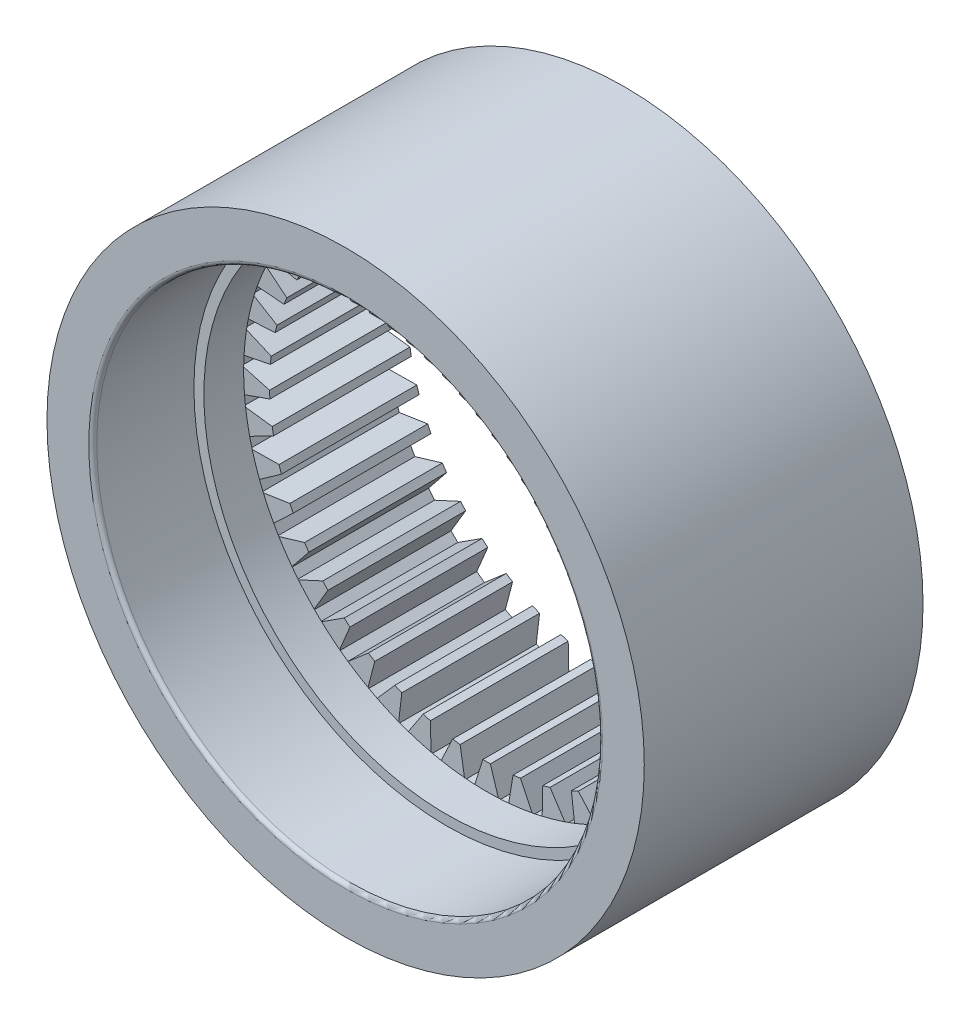
SolidWorks part; units mm, degrees
ref_plane "Plan de face" through (0, 0, 0) normal (0, 0, 1) x (1, 0, 0)
ref_plane "Plan de dessus" through (0, 0, 0) normal (0, 1, 0) x (1, 0, 0)
ref_plane "Plan de droite" through (0, 0, 0) normal (1, 0, 0) x (0, 0, -1)
sketch "Esquisse1" plane through (0, 0, 0) normal (0, 0, 1) x (1, 0, 0)
  circle A0 centre (0, 0) radius 75
  dimension "D1" = 150
extrude "Boss.-Extru.1" add sketch "Esquisse1" along normal blind 70
sketch "Esquisse2" plane through (0, 0, 70) normal (0, 0, 1) x (1, 0, 0)
  circle A0 centre (0, 0) radius 63.5
  dimension "D1" = 127
extrude "Enlèv. mat.-Extru.1" cut sketch "Esquisse2" against normal blind 25.4
sketch "Esquisse3" plane through (0, 0, 44.6) normal (0, 0, 1) x (1, 0, 0)
  circle A0 centre (0, 0) radius 54.5
  dimension "D1" = 109
extrude "Enlèv. mat.-Extru.3" cut sketch "Esquisse3" against normal through all
sketch "Esquisse4" plane through (0, 0, 44.6) normal (0, 0, 1) x (1, 0, 0)
  line L0 (0, 0) -> (0, 94.0639) construction
  line L1 (0, 0) -> (-2.8523, 54.4253)
  line L2 (-2.8523, 54.4253) -> (-1.2, 61.4253)
  line L3 (-1.2, 61.4253) -> (1.2, 61.4253)
  line L4 (2.8523, 54.4253) -> (1.2, 61.4253)
  line L5 (0, 0) -> (2.8523, 54.4253)
  line L6 (2.8523, 54.4253) -> (-9.2115, 54.4253) construction
  circle A0 centre (0, 0) radius 54.5 construction
  point P9 (0, 61.4253)
  dimension "D1" = 3
  dimension "D2" = 1.2
  dimension "10" = 7
extrude "Enlèv. mat.-Extru.4" cut sketch "Esquisse4" against normal blind 70 from offset 10 offset against normal yes
ref_axis "Axe1" through (0, 0, 70) along (0, 0, -1)
pattern_circular "Répétition circulaire1" count 45 every 8 about axis through (0, 0, 70) along (0, 0, -1) of "Enlèv. mat.-Extru.4"
sketch "Esquisse5" plane through (0, 0, 70) normal (0, 0, 1) x (1, 0, 0)
  circle A0 centre (0, 0) radius 61
  dimension "D1" = 122
extrude "Enlèv. mat.-Extru.5" cut sketch "Esquisse5" against normal blind 10 from offset 25.4 offset against normal yes
fillet "Congé1" radius 1 1 edges at (63.5, 0, 70)
ref_plane "Plan1" through (55.7347, 25.8485, 34.6) normal (-0.4384, 0.8988, 0) x (0.8988, 0.4384, 0)
equation "\"D\"= 150"
equation "\"Roulepiss\"= 25.4"
equation "\"episs\"=70"
equation "\"RoulDext\"= 127"
equation "\"D1@Esquisse1\"=\"D\""
equation "\"D1@Boss.-Extru.1\"=\"episs\""
equation "\"D1@Esquisse2\"=\"RoulDext\""
equation "\"D1@Enlèv. mat.-Extru.1\"=\"Roulepiss\""
equation "\"RoulDint\"= 109"
equation "\"D1@Esquisse3\"=\"RoulDint\""
equation "\"D1@Enlèv. mat.-Extru.4\"=\"episs\""
equation "\"D1@Enlèv. mat.-Extru.5\"=10"
